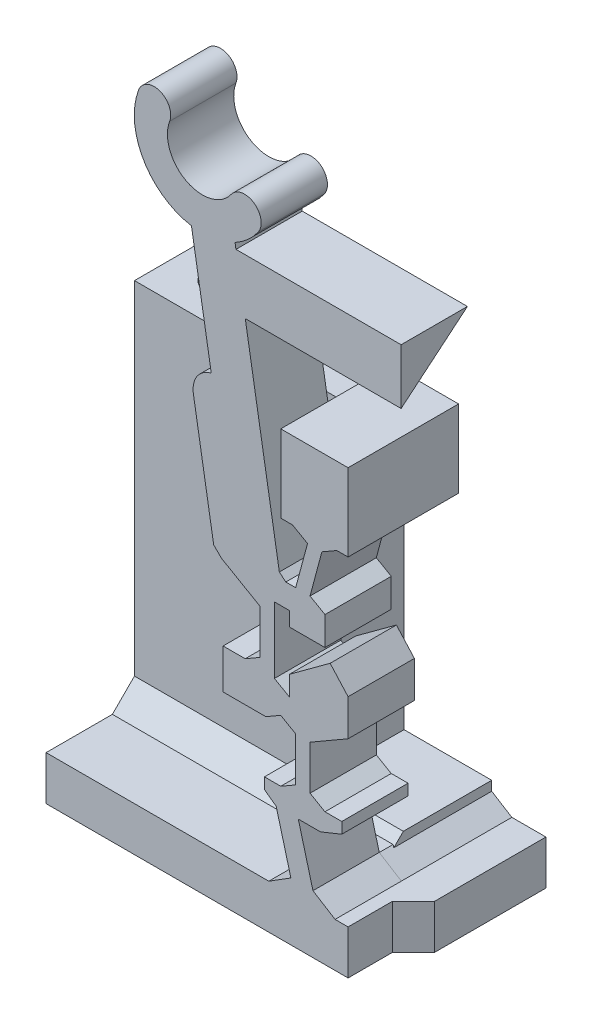
SolidWorks part; units mm, degrees
material "Nylon 6/12"
ref_plane "Front Plane" through (0, 0, 0) normal (0, 0, 1) x (1, 0, 0)
ref_plane "Top Plane" through (0, 0, 0) normal (0, 1, 0) x (1, 0, 0)
ref_plane "Right Plane" through (0, 0, 0) normal (1, 0, 0) x (0, 0, -1)
sketch "Sketch-SkeletonConfigUp" plane through (0, 0, 0) normal (0, 0, 1) x (1, 0, 0)
  line L0 (0, 0) -> (0, -50000) construction
  line L1 (0, 0) -> (4.5811, 6.2164) construction
  line L2 (9.8143, 13.3177) -> (4.5811, 13.945) construction
  line L3 (4.5811, 13.945) -> (2.9713, 10.4094) construction
  line L4 (2.9713, 10.4094) -> (4.5811, 6.2164) construction
  line L5 (4.5811, 13.945) -> (6.2429, 19.1409) construction
  line L6 (2.9713, 10.4094) -> (0.0405, 27.8193) construction
  line L7 (4.5811, 6.2164) -> (9.8143, 13.3177) construction
  line L8 (-587.3593, -797.0242) -> (9.8143, 13.3177) construction
  dimension "D2" = 7.7221
  dimension "D3" = 8.8212
  dimension "D4" = 5.2707
  dimension "D5" = 119.553
  dimension "D6" = 3.8848
  dimension "D7" = 5.4552
  dimension "D8" = 17.6549
  dimension "D9" = 4.4914
  dimension "D10" = 6.745
  dimension "D11" = 145.964
  dimension "D12" = 143.612
sketch "Sketch-SkeletonConfigDown" plane through (0, 0, 0) normal (0, 0, 1) x (1, 0, 0)
  line L0 (0, 0) -> (0, -50000) construction
  line L1 (0, 0) -> (4.5811, 6.2164) construction
  line L2 (9.8143, 13.3177) -> (4.5811, 13.945) construction
  line L3 (4.5811, 13.945) -> (6.1909, 10.4094) construction
  line L4 (6.1909, 10.4094) -> (4.5811, 6.2164) construction
  line L5 (4.5811, 13.945) -> (1.753, 18.6098) construction
  line L6 (6.1909, 10.4094) -> (-8.8652, 19.6294) construction
  line L7 (4.5811, 6.2164) -> (9.8143, 13.3177) construction
  line L8 (-589.9357, -800.5203) -> (9.8143, 13.3177) construction
  dimension "D2" = 7.7221
  dimension "D3" = 8.8212
  dimension "D4" = 5.2707
  dimension "D5" = 119.553
  dimension "D6" = 3.8848
  dimension "D7" = 5.4552
  dimension "D8" = 17.6549
  dimension "D9" = 4.4914
  dimension "D10" = 6.745
  dimension "D11" = 145.964
  dimension "D1" = 143.612
ref_plane "Plane-Cam Base" through (9.128, 0, 0) normal (1, 0, 0) x (0, 0, -1)
ref_plane "Plane-Down-to-Up Derailleur Clearance" through (6.628, 0, 0) normal (1, 0, 0) x (0, 0, -1)
ref_plane "Plane-Cam Cavity Roof" through (5.128, 0, 0) normal (1, 0, 0) x (0, 0, -1)
sketch "Sketch-SwitchBossUp" plane through (0, 0, 0) normal (0, 0, 1) x (1, 0, 0)
  line L0 (3.5811, 11.4759) -> (3.5811, 12.945) construction
  line L5 (5.5811, 12.5552) -> (5.5811, 11.263)
  line L7 (1.5115, 25.1048) -> (1.5536, 24.8548)
  line L8 (-0.4607, 24.7728) -> (0.4359, 19.4465)
  line L9 (2.9713, 10.4094) -> (0.0405, 27.8193) construction
  line L11 (0.1364, 21.2256) -> (2.1086, 21.5576) construction
  line L15 (6.628, -23.7286) -> (6.628, 23.7286) construction
  line L16 (2.9713, 10.4094) -> (4.5811, 6.2164) construction
  line L17 (3.5811, 12.945) -> (3.5811, 14.945) construction
  line L18 (5.5811, 12.945) -> (5.5811, 14.945) construction
  line L19 (4.2561, 13.945) -> (4.9061, 13.945) construction
  line L20 (3.5811, 14.945) -> (5.5811, 14.945) construction
  line L21 (3.5811, 12.945) -> (5.5811, 12.945) construction
  line L22 (4.5811, 12.945) -> (4.5811, 14.945) construction
  line L23 (4.5811, 6.2164) -> (8.5405, 7.1023) construction
  line L24 (1.9713, 9.4094) -> (1.9713, 11.4094) construction
  line L25 (3.9713, 9.4094) -> (3.9713, 11.4094) construction
  line L26 (3.9713, 9.4094) -> (1.9713, 9.4094) construction
  line L27 (1.9713, 11.4094) -> (3.9713, 11.4094) construction
  line L28 (3.5811, 7.2164) -> (5.5811, 7.2164) construction
  line L29 (3.5811, 7.2164) -> (3.5811, 5.2164) construction
  line L30 (5.5811, 7.2164) -> (5.5811, 5.2164) construction
  line L31 (3.5811, 5.2164) -> (5.5811, 5.2164) construction
  line L32 (4.9061, 6.2164) -> (4.2561, 6.2164) construction
  line L40 (3.2963, 10.4094) -> (2.6463, 10.4094) construction
  line L66 (0.0405, 27.8193) -> (0.0405, 50027.8193) construction
  line L74 (0.5455, 12.7717) -> (-0.3728, 18.2264)
  line L75 (0.3841, 13.7302) -> (2.3564, 14.0622) construction
  line L76 (5.5811, 11.263) -> (5.5811, 12.5552) construction
  line L77 (5.5811, 7.6061) -> (6.628, 8.2105)
  line L80 (5.8152, 10.763) -> (6.628, 9.8603)
  line L81 (9.128, 1033.2419) -> (9.128, 20.0586) construction
  line L85 (6.9307, 9.5241) -> (8.5405, 7.7363) construction
  line L88 (5.7256, 18.8347) -> (6.628, 18.8347)
  line L92 (3.7762, 8.3129) -> (6.9307, 9.5241) construction
  line L98 (1.9713, 9.0197) -> (0.9713, 9.0197)
  line L99 (0.9713, 9.0197) -> (0.9713, 7.2164)
  line L100 (0.9713, 7.2164) -> (2.9061, 7.2164)
  line L101 (4.5811, 6.2164) -> (6.9307, 9.5241) construction
  line L103 (0.0405, 27.8193) -> (1.9448, 26.4638) construction
  line L104 (6.9307, 9.5241) -> (8.5405, 7.7363) construction
  line L107 (1.9713, 9.4094) -> (1.9713, 9.0197) construction
  line L109 (0.0405, 27.8193) -> (-2.1498, 28.6358) construction
  line L111 (6.628, 9.8603) -> (6.628, 8.2105)
  line L112 (6.628, 9.8603) -> (6.9307, 9.5241) construction
  line L113 (2.8424, 4.8267) -> (2.8424, 4.3267)
  line L114 (7.3693, 7.7363) -> (7.3563, 7.7363) construction
  line L121 (5.0383, -1.1653) -> (5.0383, 1.4614) construction
  line L122 (3.2963, 8.9094) -> (3.9713, 8.5197)
  line L127 (5.5811, 15.3347) -> (5.5811, 14.945) construction
  line L130 (6.0388, 0.837) -> (6.628, 0.837)
  line L132 (2.8424, 4.3267) -> (3.3749, 3.937)
  line L133 (2.9713, 10.4094) -> (6.1909, 10.4094) construction
  line L134 (4.5811, 10.4094) -> (4.5811, 13.945) construction
  line L135 (4.5811, 10.4094) -> (4.5811, 6.2164) construction
  line L136 (0.8973, 12.4192) -> (0.5455, 12.7717)
  line L137 (3.9713, 9.4094) -> (5.5811, 7.2164) construction
  line L139 (5.8152, 10.763) -> (3.9713, 9.4094)
  line L141 (4.0386, 1.4604) -> (3.0388, 0.8347)
  line L142 (3.0388, 0.8347) -> (3.0388, -1.1653)
  line L143 (9.128, 20.0586) -> (9.128, 18.3333) construction
  line L145 (9.128, 16.6071) -> (9.128, -49992.4167) construction
  line L147 (5.5811, 11.263) -> (5.5811, 12.5552) construction
  line L150 (3.0388, -1.1653) -> (5.0383, -1.1653)
  line L151 (3.3749, 3.937) -> (4.3749, 3.937) construction
  line L152 (4.792, 14.945) -> (4.2561, 12.945)
  line L153 (5.442, 14.945) -> (4.9061, 12.945)
  line L157 (3.5811, 18.8347) -> (3.5811, 15.3347)
  line L158 (6.117, 15.3347) -> (6.628, 15.3347)
  line L162 (3.2963, 11.4094) -> (3.2963, 9.4094)
  line L164 (2.6463, 11.4094) -> (2.6463, 9.4094)
  line L169 (4.2561, 7.2164) -> (4.2561, 5.2164)
  line L170 (4.9061, 5.2164) -> (4.9061, 7.2164)
  line L175 (4.2561, 7.2164) -> (3.5811, 7.6061)
  line L176 (4.9061, 7.2164) -> (5.5811, 7.6061)
  line L177 (5.5811, 7.2164) -> (5.5811, 7.6061) construction
  line L179 (4.2561, 5.2164) -> (3.5811, 4.8267)
  line L180 (3.5811, 5.2164) -> (3.5811, 4.8267) construction
  line L181 (3.5811, 4.8267) -> (2.8424, 4.8267)
  line L183 (4.9061, 5.2164) -> (5.5811, 4.8267)
  line L184 (5.5811, 5.2164) -> (5.5811, 4.8267) construction
  line L186 (9.128, -23.7286) -> (9.128, 23.7286) construction
  line L187 (2.6463, 9.4094) -> (1.9713, 9.0197)
  line L190 (2.6463, 11.4094) -> (0.8973, 12.4192)
  line L191 (3.9713, 11.9094) -> (3.9713, 11.263)
  line L193 (4.9061, 12.945) -> (5.5811, 12.5552)
  line L194 (4.2561, 12.945) -> (3.8085, 12.9451)
  line L195 (3.9713, 11.263) -> (5.5811, 11.263)
  line L196 (3.9713, 9.4094) -> (3.9713, 8.5197)
  line L197 (3.5811, 7.2164) -> (3.5811, 7.6061) construction
  line L199 (3.5811, 7.6061) -> (2.9061, 7.2164)
  line L201 (2.8424, 4.3267) -> (2.8424, 3.937) construction
  line L202 (2.8424, 3.937) -> (3.3749, 3.937) construction
  line L204 (5.0383, 1.437) -> (3.0388, 1.437) construction
  line L205 (3.0388, 1.437) -> (3.0388, 0.8347) construction
  line L206 (5.0383, 1.4614) -> (6.0388, 0.837)
  line L207 (9.128, 18.3333) -> (9.128, 16.6071) construction
  line L208 (6.628, -1.1653) -> (6.628, 0.837)
  line L209 (9.128, 20.0586) -> (9.128, 16.6071) construction
  line L211 (5.0383, 1.4614) -> (4.3749, 3.937)
  line L212 (4.0386, 1.4604) -> (3.3749, 3.937)
  line L214 (4.792, 14.945) -> (4.1169, 15.3347)
  line L215 (4.1169, 15.3347) -> (3.5811, 15.3347)
  line L216 (5.442, 14.945) -> (6.117, 15.3347)
  line L217 (5.5811, 12.945) -> (5.5811, 12.5552) construction
  line L218 (5.442, 14.945) -> (5.442, 15.3347) construction
  line L219 (6.117, 15.3347) -> (4.1169, 15.3347) construction
  line L221 (9.028, 22.3548) -> (9.028, 24.8548)
  line L224 (3.5811, 18.8347) -> (5.7256, 18.8347)
  line L232 (6.628, 15.3347) -> (6.628, 18.8347)
  line L233 (6.628, -1.1653) -> (5.0383, -1.1653)
  line L236 (1.5536, 24.8548) -> (9.028, 24.8548)
  line L240 (4.3749, 3.937) -> (5.3749, 3.937)
  line L241 (5.3749, 3.937) -> (6.3424, 4.3267)
  line L248 (9.028, 22.3548) -> (1.9744, 22.3548)
  line L249 (1.9744, 22.3548) -> (3.517, 13.1918)
  line L250 (3.2963, 11.9094) -> (3.9713, 11.9094)
  line L251 (3.2963, 11.4094) -> (3.2963, 11.9094)
  line L252 (3.2963, 9.4094) -> (3.2963, 8.9094)
  line L253 (3.517, 13.1918) -> (3.8085, 12.9451)
  line L367 (5.5811, 4.8267) -> (6.3424, 4.8267)
  line L368 (6.3424, 4.8267) -> (6.3424, 4.3267)
  arc A0 (1.5115, 25.1048) -> (2.5558, 26.0289) centre (0.0405, 27.8193) ccw
  arc A1 (-0.4607, 24.7728) -> (-2.8525, 28.8978) centre (0.0405, 27.8193) cw
  arc A2 (-2.8525, 28.8978) -> (-1.447, 28.3738) centre (-2.1498, 28.6358) cw
  arc A3 (2.5558, 26.0289) -> (1.3338, 26.8987) centre (1.9448, 26.4638) ccw
  arc A4 (-1.447, 28.3738) -> (1.3338, 26.8987) centre (0.0405, 27.8193) ccw
  arc A5 (3.5811, 12.945) -> (3.5811, 14.945) centre (3.1778, 13.945) ccw construction
  arc A6 (5.5811, 12.945) -> (5.5811, 14.945) centre (5.9843, 13.945) cw construction
  arc A7 (2.5293, 9.921) -> (1.9713, 11.4094) centre (1.568, 10.4094) ccw construction
  arc A8 (3.9713, 11.4094) -> (3.9713, 9.4094) centre (4.3745, 10.4094) ccw construction
  arc A9 (3.5811, 7.2164) -> (3.5811, 5.2164) centre (3.1779, 6.2164) cw construction
  arc A10 (5.5811, 7.2164) -> (5.5811, 5.2164) centre (5.9844, 6.2164) ccw construction
  arc A19 (-0.3728, 18.2264) -> (0.4359, 19.4465) centre (0.6836, 18.4042) cw
  circle A28 centre (0.0405, 27.8193) radius 2.3375 construction
  arc A29 (1.9713, 9.4094) -> (2.5293, 9.921) centre (1.568, 10.4094) ccw construction
  point P53 (4.5811, 13.945)
  point P63 (2.9713, 10.4094)
  point P93 (1.1225, 21.3916)
  point P156 (3.5585, 12.9452)
  dimension "D23" = 1.5875
  dimension "D24" = 0.75
  dimension "D2" = 2
  dimension "D5" = 2
  dimension "D6" = 0.65
  dimension "D8" = 42
  dimension "D16" = 42
  dimension "D27" = 120
  dimension "D28" = 120
  dimension "D29" = 120
  dimension "D30" = 120
  dimension "D31" = 120
  dimension "D34" = 120
  dimension "D17" = 0.5
  dimension "D21" = 3.5
  dimension "D22" = 1
  dimension "D38" = 2
  dimension "D39" = 0.5
  dimension "D40" = 60
  dimension "D41" = 1
  dimension "D42" = 45
  dimension "D43" = 120
  dimension "D10" = 15
  dimension "D12" = 2.5
  dimension "D13" = 1
  dimension "D19" = 1
  dimension "D25" = 15
  dimension "D26" = 120
  dimension "D35" = 120
  dimension "D20" = 3
  dimension "D48" = 2
  dimension "D49" = 0.6
  dimension "D82" = 1
  dimension "D83" = 3.5
  dimension "D14" = 2.5
  dimension "D15" = 0.25
extrude "Boss-Switch Body" add sketch "Sketch-SwitchBossUp" along normal blind 3
sketch "Sketch1" plane through (0, 0, 0) normal (0, 0, -1) x (-1, 0, 0)
  line L1 (-7.5811, -1.1653) -> (0.4122, -1.1653)
  line L2 (-7.5811, -1.1653) -> (-7.5811, 0.837)
  line L4 (0.4122, -1.1653) -> (0.4122, 0.8347)
  line L5 (-3.5811, 18.8347) -> (-7.5811, 18.8347)
  line L10 (-7.5811, 18.8347) -> (-7.5811, 15.3347)
  line L11 (-4.0386, 1.4604) -> (-5.0386, 1.4604)
  line L12 (-7.5811, 15.3347) -> (-3.5811, 15.3347)
  line L13 (-4.0386, 1.4604) -> (-3.0388, 0.8347)
  line L14 (-3.5811, 15.3347) -> (-3.5811, 18.8347)
  line L20 (-4.3749, 3.937) -> (-5.0383, 1.4614) construction
  line L22 (-3.0388, -1.1653) -> (-6.628, -1.1653) construction
  line L23 (-3.0388, 0.8347) -> (0.4122, 0.8347)
  line L24 (-5.0386, 1.4604) -> (-6.0388, 0.837)
  line L25 (-6.0388, 0.837) -> (-7.5811, 0.837)
  dimension "D1" = 3.5
extrude "Boss-Flange Width" add sketch "Sketch1" along normal blind 5
ref_plane "Plane-Sta2Sit Groove" through (0.0405, 0, 0) normal (1, 0, 0) x (0, 0, -1)
ref_plane "Plane-Cam Outer Surface" through (-12.0395, 0, 0) normal (1, 0, 0) x (0, 0, -1)
ref_plane "Plane-FlangeTop" through (-7.0395, 0, 0) normal (1, 0, 0) x (0, 0, -1)
sketch "Sketch2" plane through (-7.0395, 0, 0) normal (1, 0, 0) x (0, 0, -1)
  line L0 (5, 15.3347) -> (-3, 15.3347) construction
  line L1 (5, 17.3347) -> (1, 17.3347)
  line L2 (5, 17.3347) -> (5, 15.3347)
  line L3 (5, 15.3347) -> (1, 15.3347)
  line L4 (1, 17.3347) -> (1, 15.3347)
  line L5 (-3, -1.1653) -> (-3, 0.837) construction
  line L11 (5, 0.8347) -> (-3, 0.8347)
  line L12 (5, 0.8347) -> (5, -1.1653)
  line L13 (5, -1.1653) -> (-3, -1.1653)
  line L14 (-3, 0.8347) -> (-3, -1.1653)
  line L15 (0, 10.4094) -> (0, 27.8193) construction
  line L17 (5, 0.837) -> (5, -1.1653) construction
  line L18 (-3, 0.8347) -> (0, 0.8347) construction
  dimension "D1" = 1
  dimension "D2" = 2
extrude "Boss-Flange Height" add sketch "Sketch2" along normal up to surface (11.6675 mm away)
sketch "Sketch10" plane through (0, 15.3347, 0) normal (0, 1, 0) x (1, 0, 0)
  line L0 (9.128, -23.7286) -> (9.128, 23.7286) construction
  line L1 (7.5811, 5) -> (5.128, 5)
  line L2 (7.5811, 5) -> (7.5811, 2)
  line L3 (7.5811, 2) -> (5.128, 2)
  line L5 (4.628, 7) -> (4.628, 1) construction
  line L6 (3.5811, 1) -> (-7.0395, 1) construction
  line L8 (5.128, 5) -> (5.128, 2)
  dimension "D1" = 1
  dimension "D2" = 0.5
  dimension "D3" = 4.5
extrude "Cut-Up-To-Down Derailleur Clearance" cut sketch "Sketch10" along normal up to next
sketch "Sketch17" plane through (0, 15.3347, 0) normal (0, -1, 0) x (1, 0, 0)
  line L0 (5.128, -5) -> (-7.0395, -5)
  line L1 (5.128, -5) -> (-7.0395, -5) construction
  line L2 (-7.0395, -5) -> (-7.0395, -1)
  line L3 (-7.0395, -1) -> (5.128, -1)
  line L4 (5.128, -1) -> (5.128, -5)
  line L5 (-7.0395, -1) -> (-7.0395, -5) construction
extrude "Boss-Flange Support" add sketch "Sketch17" along normal up to surface (14.5 mm away) up to face at (-2.0003, 0.8347, -1)
sketch "Sketch-HolePositions" plane through (0, -1.1653, 0) normal (0, -1, 0) x (1, 0, 0)
  line L0 (-7.0395, -3) -> (7.5811, -3) construction
  line L1 (7.5811, -5) -> (-7.0395, -5) construction
  line L2 (7.5811, -5) -> (7.5811, 0) construction
  line L4 (-7.0395, -22.2167) -> (-7.0395, 22.2167) construction
  point P6 (-5.0395, -3)
  point P7 (-0.5395, -3)
  dimension "D1" = 2
  dimension "D2" = 4.5
  dimension "D3" = 2
sketch "Sketch6" plane through (0, -1.1653, 0) normal (0, -1, 0) x (-1, 0, 0)
  point P0 (5.0395, 3)
  point P3 (0.5395, 3)
hole_wizard "Tap Drill for M2x0.4 Tap1" positions "Sketch6" profile "Sketch5" hole size "M2x0.4" standard "ANSI Metric" end condition through all
sketch "Sketch5" plane through (-5.0395, -1.1653, -3) normal (1, 0, 0) x (0, 0, -1)
  line L0 (0, 0) -> (0, 30.5511)
  line L1 (0, 30.5511) -> (0.8, 30.5511)
  line L2 (0.8, 30.5511) -> (0.8, 0)
  line L5 (0.8, 0) -> (0, 0)
  line L11 (0, -6.35) -> (0, 107.95) construction
  dimension "Thru Hole Dia." = 1.6
  dimension "Thru Hole Depth" = 30.5511
sketch "Sketch9" plane through (0, -1.1653, 0) normal (0, -1, 0) x (1, 0, 0)
  point P0 (-5.0395, -3)
  point P3 (-0.5395, -3)
hole_wizard "M2 Clearance Hole2" positions "Sketch9" profile "Sketch8" hole size "M2" standard "ANSI Metric"
sketch "Sketch8" plane through (-5.0395, -1.1653, -3) normal (1, 0, 0) x (0, 0, -1)
  line L0 (0, 0) -> (0, 15.721)
  line L1 (0, 15.721) -> (1.2, 15)
  line L2 (1.2, 15) -> (1.2, 0)
  line L5 (1.2, 0) -> (0, 0)
  line L10 (0, 15.721) -> (-1.2, 15) construction
  line L11 (0, -6.35) -> (0, 107.95) construction
  dimension "Hole Dia." = 2.4
  dimension "Hole Depth" = 15
  dimension "Drill Angle" = 118
sketch "Sketch-Measurements for Derailleur Ramps" [suppressed] plane through (0, 0, 0) normal (0, 0, 1) x (1, 0, 0)
  line L0 (3.184, 15.1695) -> (2.4687, 19.4188)
  line L1 (2.8264, 17.2941) -> (1.8402, 17.1281)
  line L2 (2.9713, 10.4094) -> (0.0405, 27.8193) construction
  line L3 (1.8402, 17.1281) -> (-1.3081, 15.0016)
  line L4 (6.1909, 10.4094) -> (-8.8652, 19.6294) construction
  line L5 (1.8402, 17.1281) -> (2.6012, 12.6077)
  line L6 (2.6012, 12.6077) -> (-1.3081, 15.0016)
  line L7 (0.2661, 16.0649) -> (0.2661, 17.1281)
  line L8 (0.2661, 17.1281) -> (1.8402, 17.1281)
  line L9 (6.1909, 10.4094) -> (2.9713, 10.4094)
  line L10 (5.386, 8.3129) -> (3.7762, 8.3129)
  line L11 (2.6116, 18.5698) -> (1.5115, 25.1048) construction
  line L12 (6.1909, 10.4094) -> (4.5811, 6.2164) construction
  line L13 (4.5811, 8.3129) -> (4.5811, 8.7912)
  line L14 (4.5811, 6.2164) -> (5.386, 8.3129)
  line L15 (2.9713, 10.4094) -> (4.5811, 6.2164) construction
  line L16 (3.7762, 8.3129) -> (4.5811, 6.2164)
  line L17 (5.386, 8.3129) -> (5.386, 8.7912)
  dimension "D1" = 1.5742
  dimension "D2" = 0.8049
ref_plane "Plane1" through (0, 7.1023, 0) normal (0, 1, 0) x (1, 0, 0)
ref_plane "Plane-Cantilever Cut" [suppressed] through (7.0848, 8.5204, -1.9058) normal (-0.6301, -0.7578, 0.1695) x (-0.7765, 0.6151, -0.1368)
sketch "Sketch14" [suppressed] plane through (7.0848, 8.5204, -1.9058) normal (-0.6301, -0.7578, 0.1695) x (-0.7765, 0.6151, -0.1368)
  line L0 (2.3023, -1.6911) -> (-0.3551, -1.6911)
  line L2 (2.3023, -4.3362) -> (2.3023, -1.6911)
  line L3 (-0.3551, -1.6911) -> (-0.3551, -4.4608)
  line L5 (-0.3551, -4.4608) -> (1.0087, -5.0843)
  line L6 (1.0087, -5.0843) -> (2.3023, -4.3362)
extrude "Cut-Down-to-Up Cantilever Slope" [suppressed] cut sketch "Sketch14" against normal up to next
ref_plane "Plane-Symmetry Plane" through (0, 0, 1.5) normal (0, 0, 1) x (1, 0, 0)
sketch "Sketch-Cable Center Point" plane through (0, 0, 1.5) normal (0, 0, 1) x (1, 0, 0)
  line L0 (0.0405, 27.8193) -> (0.1722, 27.0366)
  line L1 (2.9713, 10.4094) -> (0.0405, 27.8193) construction
  point P0 (0.0405, 27.8193)
  dimension "D1" = 0.7937
chamfer "Chamfer-Flange Support" distance 1.5 angle 45 1 edges at (3.5811, 17.3347, -3)
chamfer "Chamfer-Flange Support 2" distance 1.5 angle 45 2 edges at (5.128, 17.0847, -2) (5.128, 15.3347, -1.5)
chamfer "Chamfer-Flange Support 3" distance 1 angle 45 1 edges at (-2.0003, 0.8347, -1)
chamfer "Chamfer7" [suppressed] distance 1 angle 45
sketch "Sketch23" plane through (0, 0, -1) normal (0, 0, 1) x (1, 0, 0)
  line L0 (5.128, 1.8347) -> (1.1605, 1.8347)
  line L1 (-7.0395, 1.8347) -> (5.128, 1.8347) construction
  line L2 (1.1605, 1.8347) -> (1.1605, 13.8347)
  line L3 (1.1605, 13.8347) -> (5.128, 13.8347)
  line L4 (5.128, 13.8347) -> (5.128, 1.8347)
  line L5 (0.6605, -1.1653) -> (0.6605, 13.8347) construction
  dimension "D1" = 0.5
extrude "Cut-Gap for Printing" cut sketch "Sketch23" against normal through all
sketch "Sketch25" plane through (0, 0, 0) normal (0, 0, 1) x (1, 0, 0)
  line L0 (6.628, 15.3347) -> (7.5811, 15.3347)
  line L1 (7.5811, 15.3347) -> (7.5811, 18.8347)
  line L2 (7.5811, 18.8347) -> (6.628, 18.8347)
  line L3 (6.628, -23.7286) -> (6.628, 23.7286) construction
  line L4 (7.5811, 18.8347) -> (3.5811, 18.8347) construction
  line L5 (6.628, 18.8347) -> (6.628, 15.3347)
  line L6 (7.5811, 18.8347) -> (7.5811, 15.3347) construction
  point P4 (0, 0)
  point P12 (7.5811, 18.8347)
extrude "Cut-Derailleur Clearance" cut sketch "Sketch25" against normal through all
chamfer "Chamfer8" distance 1 angle 45 1 edges at (6.628, -0.1641, 0)
ref_plane "Plane2" through (-5.9548, 8.4004, 7.0004) normal (0.4783, -0.6747, -0.5622) x (-0.8782, -0.3674, -0.3062)
sketch "Sketch26" plane through (-5.9548, 8.4004, 7.0004) normal (0.4783, -0.6747, -0.5622) x (-0.8782, -0.3674, -0.3062)
  line L0 (-12.9549, 15.9117) -> (-12.9549, 12.0065)
  line L1 (-17.0603, 15.9117) -> (-10.4961, 15.9117) construction
  line L2 (-10.8657, 12.0065) -> (-17.0603, 12.0065) construction
  line L3 (-12.9549, 12.0065) -> (-20.0302, 12.0065)
  line L4 (-20.0302, 12.0065) -> (-20.0302, 15.9117)
  line L5 (-20.0302, 15.9117) -> (-12.9549, 15.9117)
extrude "Cut-Extrude1" cut sketch "Sketch26" along normal up to next
sketch "Sketch27" plane through (5.128, 0, 0) normal (1, 0, 0) x (0, 0, -1)
  line L0 (3.5, 18.8347) -> (3.5, 13.8347) construction
  line L1 (3, 18.8347) -> (5, 18.8347)
  line L2 (3, 18.8347) -> (3, 13.8347)
  line L3 (3, 13.8347) -> (5, 13.8347)
  line L4 (5, 18.8347) -> (5, 13.8347)
  dimension "D1" = 0.5
extrude "Cut-Wide Derailleur Clearance" cut sketch "Sketch27" against normal blind 4 and the other way through all
chamfer "Chamfer9" distance 1 angle 45 1 edges at (4.6045, 18.8347, -3)
equation "\"axle-diameter\"=2"
equation "\"switch-thickness\"=12"
equation "\"base-width\"=4.0"
equation "\"axle-bushing-radius\"=3"
equation "\"clearance\"= 0.25"
equation "\"arm-width\"=1.5"
equation "\"min-diameter\"=70"
equation "\"alpha\"=143.6120"
equation "\"gamma\"=119.5526"
equation "\"delta\"=145.9637"
equation "\"epsilon\"=6.7452"
equation "\"l_AB\"=8.8212"
equation "\"l_AC\"=4.4914"
equation "\"l_BD\"=5.2707"
equation "\"l_CD\"=3.8848"
equation "\"l_CE\"=17.6549"
equation "\"l_DF\"=5.4552"
equation "\"l_OA\"=7.7221"
equation "\"D2@Sketch-SkeletonConfigUp\" = \"l_OA\""
equation "\"D3@Sketch-SkeletonConfigUp\" = \"l_AB\""
equation "\"D4@Sketch-SkeletonConfigUp\" = \"l_BD\""
equation "\"D5@Sketch-SkeletonConfigUp\" = \"gamma\""
equation "\"D6@Sketch-SkeletonConfigUp\" = \"l_CD\""
equation "\"D7@Sketch-SkeletonConfigUp\" = \"l_DF\""
equation "\"D8@Sketch-SkeletonConfigUp\" = \"l_CE\""
equation "\"D9@Sketch-SkeletonConfigUp\" = \"l_AC\""
equation "\"D_groove\"=3.175"
equation "\"D7@Sketch-SkeletonConfigDown\" = \"l_DF\""
equation "\"D6@Sketch-SkeletonConfigDown\" = \"l_CD\""
equation "\"D2@Sketch-SkeletonConfigDown\" = \"l_OA\""
equation "\"D3@Sketch-SkeletonConfigDown\" = \"l_AB\""
equation "\"D9@Sketch-SkeletonConfigDown\" = \"l_AC\""
equation "\"D8@Sketch-SkeletonConfigDown\" = \"l_CE\""
equation "\"D5@Sketch-SkeletonConfigDown\" = \"gamma\""
equation "\"D4@Sketch-SkeletonConfigDown\" = \"l_BD\""
equation "\"D1@Sketch-SkeletonConfigDown\" = \"alpha\""
equation "\"hinge_length\"=1.5"
equation "\"hinge_depth\"=0.25"
equation "\"D10@Sketch-SkeletonConfigUp\"=\"epsilon\""
equation "\"D11@Sketch-SkeletonConfigUp\"=\"delta\""
equation "\"D12@Sketch-SkeletonConfigUp\"=\"alpha\""
equation "\"D11@Sketch-SkeletonConfigDown\"=\"delta\""
equation "\"D10@Sketch-SkeletonConfigDown\"=\"epsilon\""
equation "\"EE_dx\"=8.9056"
equation "\"EE_dy\"=8.1898"
equation "\"r_groove\"=\"D_groove\"/2"
equation "\"t_wall\"=25.4/16"
equation "\"width_lower\"=\"D_groove\"+\"t_wall\""
equation "\"cable_to_bottom\"=30.6257"
equation "\"switch_EE-up_base_dy\"=24"
equation "\"switch_EE-down_base_dy\"=16"
equation "\"D_axle\"=25.4/8"
equation "\"D_up_to_down\"=16"
equation "\"D_down_to_up\"=25"
equation "\"t_cam_base\"=7.5"
equation "\"D23@Sketch-SwitchBossUp\"=\"D_groove\"/2"
equation "\"D1@Sketch-Cable Center Point\"=\"D_groove\"/4"
